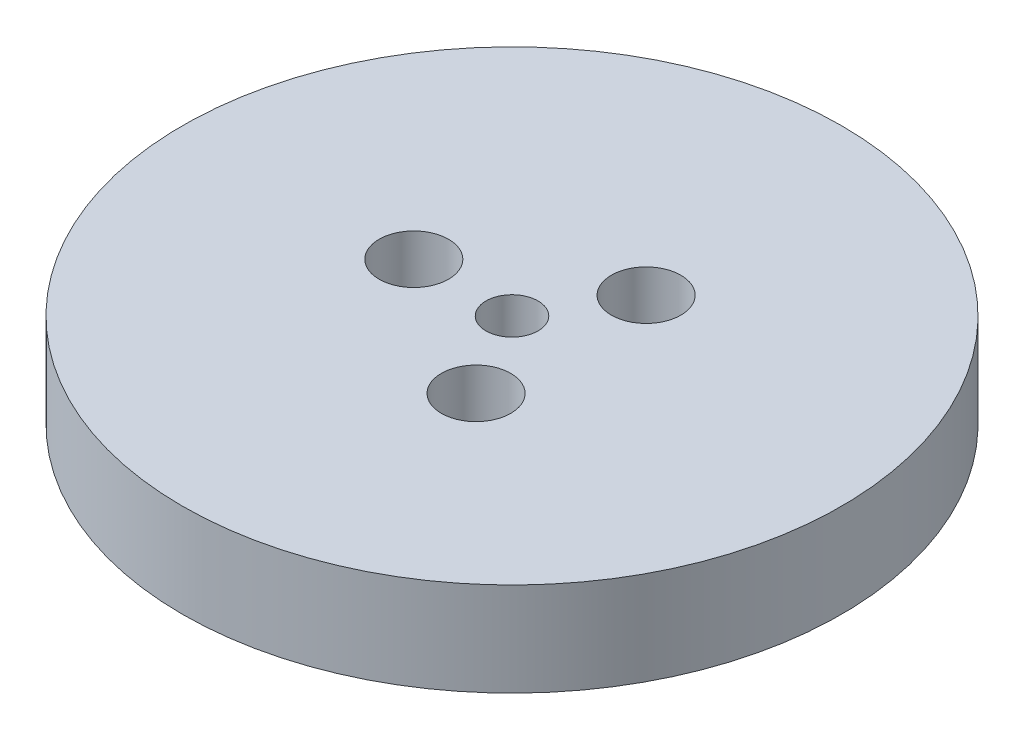
SolidWorks part; units mm, degrees
ref_plane "Front Plane" through (0, 0, 0) normal (0, 0, 1) x (1, 0, 0)
ref_plane "Top Plane" through (0, 0, 0) normal (0, 1, 0) x (1, 0, 0)
ref_plane "Right Plane" through (0, 0, 0) normal (1, 0, 0) x (0, 0, -1)
sketch "Sketch1" plane through (0, 0, 0) normal (0, 1, 0) x (1, 0, 0)
  circle A0 centre (0, 0) radius 95
  dimension "FLANGE_OD" = 190
extrude "Boss-Extrude1" add sketch "Sketch1" along normal blind 27
sketch "Sketch2" plane through (0, 0, 0) normal (0, 1, 0) x (1, 0, 0)
  circle A0 centre (0, 0) radius 7.5
  dimension "BORE_D" = 15
extrude "Cut-Extrude1" cut sketch "Sketch2" along normal through all
sketch "Sketch3" plane through (0, 27, 0) normal (0, 1, 0) x (1, 0, 0)
  circle A0 centre (0, 0) radius 28.2998 construction
  circle A1 centre (-28.2998, 0) radius 10
  dimension "BOLT_D" = 20
  dimension "BOLT_PCD" = 56.5997
extrude "Cut-Extrude2" cut sketch "Sketch3" against normal blind 22.1461
pattern_circular "CirPattern1" count 3 over 360 about axis through (0, 0, 0) along (0, 1, 0) of "Cut-Extrude2"
